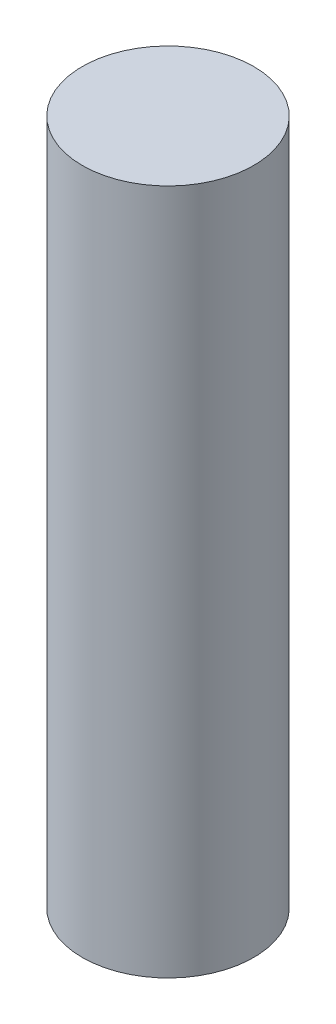
SolidWorks part; units mm, degrees
ref_plane "Front Plane" through (0, 0, 0) normal (0, 0, 1) x (1, 0, 0)
ref_plane "Top Plane" through (0, 0, 0) normal (0, 1, 0) x (1, 0, 0)
ref_plane "Right Plane" through (0, 0, 0) normal (1, 0, 0) x (0, 0, -1)
sketch "Sketch1" plane through (0, 0, 0) normal (0, 1, 0) x (1, 0, 0)
  circle A0 centre (0, 0) radius 5
  dimension "D1" = 10
extrude "Boss-Extrude1" add sketch "Sketch1" along normal blind 20 and the other way blind 20
